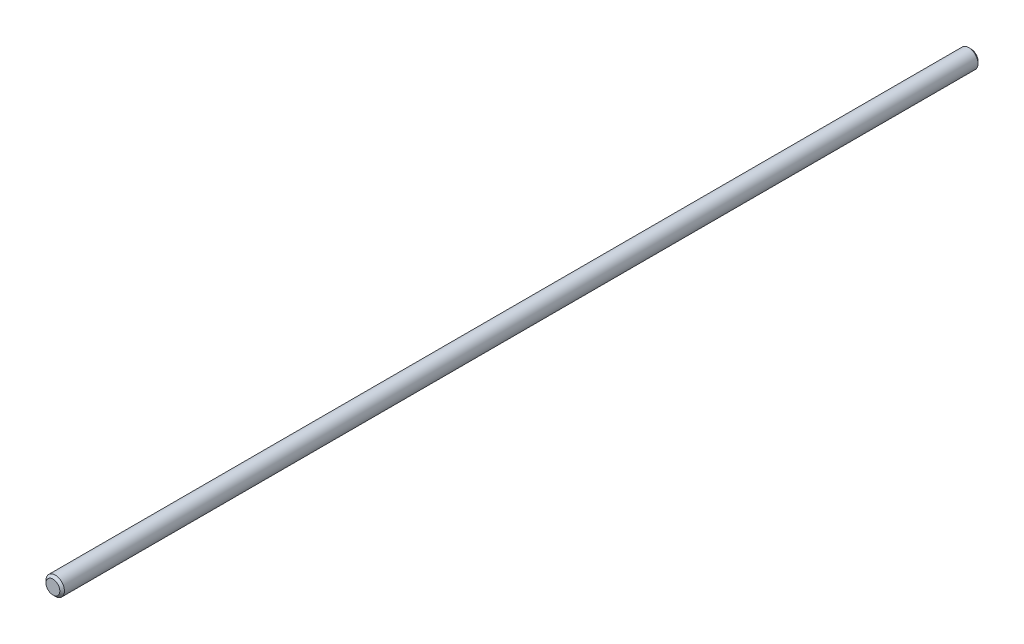
SolidWorks part; units mm, degrees
ref_plane "Piano frontale" through (0, 0, 0) normal (0, 0, 1) x (1, 0, 0)
ref_plane "Piano superiore" through (0, 0, 0) normal (0, 1, 0) x (1, 0, 0)
ref_plane "Piano destro" through (0, 0, 0) normal (1, 0, 0) x (0, 0, -1)
sketch "Schizzo1" plane through (0, 0, 0) normal (0, 0, 1) x (1, 0, 0)
  circle A0 centre (0, 0) radius 4
  dimension "D1" = 8
extrude "Estrusione-Estrusione1" add sketch "Schizzo1" along normal blind 398
chamfer "Smusso1" distance 1 angle 45 2 edges at (4, 0, 398) (4, 0, 0)
sketch "Schizzo2" plane through (0, 0, 0) normal (0, 1, 0) x (1, 0, 0)
  line L0 (4, -397) -> (4, -1) construction
  line L1 (4, -397) -> (4, -1) construction
  line L2 (4, -397) -> (-4, -397) construction
  line L3 (4, -1) -> (-4, -1) construction
